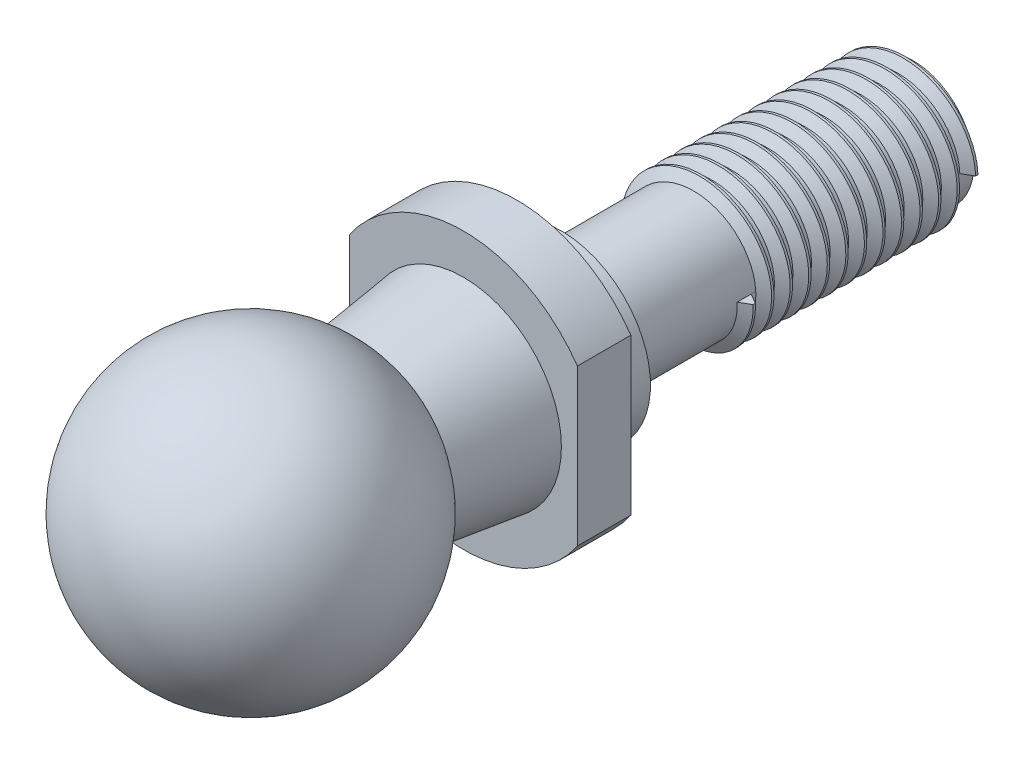
SolidWorks part; units mm, degrees
material "Cast Carbon Steel"
ref_plane "Front Plane" through (0, 0, 0) normal (0, 0, 1) x (1, 0, 0)
ref_plane "Top Plane" through (0, 0, 0) normal (0, 1, 0) x (1, 0, 0)
ref_plane "Right Plane" through (0, 0, 0) normal (1, 0, 0) x (0, 0, -1)
sketch "Sketch1" plane through (0, 0, 0) normal (1, 0, 0) x (0, 0, -1)
  line L0 (0, 8.255) -> (0, -8.255)
  arc A0 (0, 8.255) -> (0, -8.255) centre (0, 0) ccw
  dimension "D1" = 16.51
revolve "Revolve1" add sketch "Sketch1" angle 360 about L0
sketch "Sketch2" plane through (0, 0, 0) normal (1, 0, 0) x (0, 0, -1)
  line L0 (6.6564, 4.8824) -> (6.6564, 0)
  line L1 (6.6564, 0) -> (12.1382, 0)
  line L2 (12.1382, 0) -> (12.1382, 5.588)
  line L3 (12.1382, 5.588) -> (6.6564, 4.8824)
  circle A0 centre (0, 0) radius 8.255 construction
  dimension "D1" = 4.8824
  dimension "D2" = 5.588
  dimension "D3" = 5.4818
revolve "Revolve3" add sketch "Sketch2" angle 360 about L1
sketch "Sketch3" plane through (0, 0, -12.1382) normal (0, 0, -1) x (-1, 0, 0)
  line L0 (-6.4994, 4.445) -> (-6.4994, -4.445)
  line L1 (6.4994, 4.445) -> (6.4994, -4.445)
  arc A0 (-6.4994, -4.445) -> (6.4994, -4.445) centre (0, 0) ccw
  arc A1 (6.4994, 4.445) -> (-6.4994, 4.445) centre (0, 0) ccw
  dimension "D1" = 15.748
  dimension "D2" = 8.89
  dimension "D3" = 8.89
extrude "Boss-Extrude1" add sketch "Sketch3" along normal blind 3.048
sketch "Sketch4" plane through (0, 0, -15.1862) normal (0, 0, -1) x (-1, 0, 0)
  circle A0 centre (0, 0) radius 5.08
  dimension "D1" = 10.16
extrude "Boss-Extrude2" add sketch "Sketch4" along normal blind 2.54
sketch "Sketch5" plane through (0, 0, -17.7262) normal (0, 0, -1) x (-1, 0, 0)
  circle A0 centre (0, 0) radius 3.4544
  dimension "D1" = 6.9088
extrude "Boss-Extrude3" add sketch "Sketch5" along normal blind 20.066
thread "Thread1" pitch 1.0583 method extrude profile "Thread Profile1" start angle 0, offset 0, length 12.7, pitch 1.0583, diameter 6.9088
ref_plane "Plane1" through (3.4544, 0, -37.7922) normal (0, -1, 0) x (1, 0, 0)
sketch "Thread Profile1" plane through (3.4544, 0, -37.7922) normal (0, -1, 0) x (1, 0, 0)
  line L0 (0, 0) -> (0, 1.0583) construction
  line L1 (0, 0) -> (0.5728, 0.3307)
  line L2 (0.5728, 0.3307) -> (0.5728, 0.463)
  line L3 (0.5728, 0.463) -> (0, 0.7937)
  line L4 (0.5728, 0.3969) -> (0, 0.3969) construction
  line L11 (0, 0) -> (0, 0.7937)
  point P2 (0, 0)
  dimension "Pitch" = 1.0583
  dimension "Profile_Angle" = 60
  dimension "Profile_Land" = 0.1323
  dimension "Profile_Height" = 0.5728
